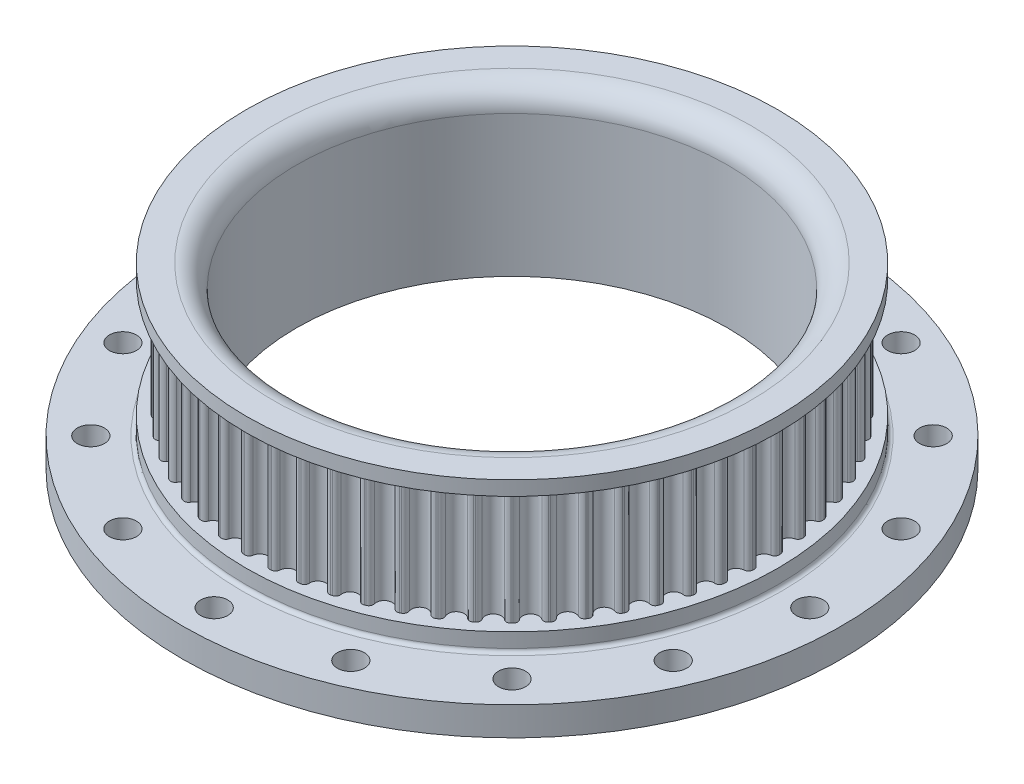
SolidWorks part; units mm, degrees
ref_plane "Front Plane" through (0, 0, 0) normal (0, 0, 1) x (1, 0, 0)
ref_plane "Top Plane" through (0, 0, 0) normal (0, 1, 0) x (1, 0, 0)
ref_plane "Right Plane" through (0, 0, 0) normal (1, 0, 0) x (0, 0, -1)
sketch "Sketch1" plane through (0, 0, 0) normal (0, 1, 0) x (1, 0, 0)
  line L0 (0, 0) -> (0, 28.2667) construction
  line L1 (0, 0) -> (2.9202, 27.7837) construction
  circle A0 centre (0, 0) radius 28.2667 construction
  circle A1 centre (0, 0) radius 27.0467 construction
  circle A2 centre (0, 27.9367) radius 0.89 construction
  circle A5 centre (2.9202, 27.7837) radius 0.89 construction
  arc A6 (0, 27.0467) -> (0.8804, 27.8061) centre (0, 27.9367) ccw
  arc A7 (0.8804, 27.8061) -> (1.3997, 28.2321) centre (1.3749, 27.7327) cw
  arc A8 (1.559, 28.2237) -> (2.031, 27.7458) centre (1.5314, 27.7245) cw
  arc A9 (2.8272, 26.8986) -> (2.031, 27.7458) centre (2.9202, 27.7837) cw
  arc A10 (1.3997, 28.2321) -> (1.559, 28.2237) centre (0, 0) cw
  arc A11 (0, 27.0467) -> (2.8272, 26.8986) centre (0, 0) ccw
  dimension "D1" = 56.5335
  dimension "D3" = 1.78
  dimension "D4" = 0.5
  dimension "D2" = 1.22
  dimension "D5" = 6
extrude "Boss-Extrude1" add sketch "Sketch1" along normal mid plane 13 contours A6 A11 A9 A8 A7 region at (0.001, 0, -0.0192)
ref_axis "Axis1" through (0, 3.3, 0) along (0, -1, 0)
pattern_circular "CirPattern1" count 60 over 360 about axis through (0, 3.3, 0) along (0, -1, 0) of "Boss-Extrude1"
sketch "Sketch2" plane through (0, 0, 0) normal (1, 0, 0) x (0, 0, -1)
  line L10 (0, 6.5) -> (29.4415, 6.5) construction
  line L11 (0, 6.5) -> (0, 8.0875) construction
  line L12 (0, 8.0875) -> (29.4415, 8.0875) construction
  line L15 (29.4415, 6.5) -> (29.4415, 8.0875) construction
  line L20 (0, 3.3) -> (0, -3.3) construction
  line L22 (29.4415, 8.0875) -> (0, 8.0875)
  line L23 (29.4415, 8.0875) -> (29.4415, 6.5)
  line L24 (29.4415, 6.5) -> (0, 6.5)
  line L25 (0, 8.0875) -> (0, 6.5)
  dimension "D1" = 1.5875
  dimension "D2" = 29.4415
  dimension "D3" = 6.5
revolve "Revolve3" add sketch "Sketch2" angle 360 about axis through (0, 3.3, 0) along (0, -1, 0) region at (0, 7.2937, -14.7207)
mirror "Mirror1" about plane through (0, 0, 0) normal (0, 1, 0) of "Revolve3"
sketch "Sketch3" plane through (0, 0, 0) normal (0, -1, 0) x (-1, 0, 0)
  circle A0 centre (0, 0) radius 23.8852
  dimension "D1" = 47.7705
extrude "Cut-Extrude1" cut sketch "Sketch3" against normal through all both and the other way through all
sketch "Sketch5" plane through (0, 0, 0) normal (0, 0, 1) x (1, 0, 0)
  line L0 (29.4415, -6.5) -> (-29.4415, -6.5) construction
  line L1 (-29.854, -8.5) -> (-36.5125, -8.5)
  line L2 (-36.5125, -8.5) -> (-36.5125, -10.0875)
  line L3 (-36.5125, -10.0875) -> (-23.8852, -10.0875)
  line L4 (-23.8852, -10.0875) -> (-23.8852, -8.0875)
  line L5 (-29.4415, -8.0875) -> (29.4415, -8.0875) construction
  line L6 (-23.8852, -8.0875) -> (-29.4415, -8.0875)
  arc A0 (-29.4415, -8.0875) -> (-29.854, -8.5) centre (-29.854, -8.0875) cw
  dimension "D1" = 2
  dimension "D2" = 36.5125
  dimension "D3" = 1.5875
revolve "Revolve4" add sketch "Sketch5" angle 360 about axis through (0, 3.3, 0) along (0, -1, 0)
sketch "Sketch6" plane through (0, -8.5, 0) normal (0, 1, 0) x (1, 0, 0)
  line L0 (-30.488, 12.6286) -> (0, 0) construction
  line L1 (0, 0) -> (-36.5125, 0) construction
  circle A0 centre (-30.488, 12.6286) radius 1.5
  circle A1 centre (0, 0) radius 36.5125 construction
  dimension "D2" = 3
  dimension "D1" = 33
  dimension "D3" = 22.5
extrude "Cut-Extrude2" cut sketch "Sketch6" against normal through all
pattern_circular "CirPattern2" count 16 over 360 about axis through (0, 3.3, 0) along (0, -1, 0) of "Cut-Extrude2"
fillet "Fillet1" radius 2.54 1 edges at (0, 8.0875, -23.8852)
sketch "Sketch9" plane through (0, -10.0875, 0) normal (0, -1, 0) x (1, 0, 0)
  circle A1 centre (0, 0) radius 36.5125
  circle A2 centre (0, 0) radius 29
  circle A3 centre (-30.488, -12.6286) radius 1.5
  circle A4 centre (-30.488, -12.6286) radius 1.5
  circle A5 centre (-23.3345, -23.3345) radius 1.5
  circle A6 centre (-23.3345, -23.3345) radius 1.5
  circle A7 centre (23.3345, 23.3345) radius 1.5
  circle A8 centre (23.3345, 23.3345) radius 1.5
  circle A9 centre (12.6286, 30.488) radius 1.5
  circle A10 centre (12.6286, 30.488) radius 1.5
  circle A11 centre (0, 33) radius 1.5
  circle A12 centre (0, 33) radius 1.5
  circle A13 centre (-12.6286, 30.488) radius 1.5
  circle A14 centre (-12.6286, 30.488) radius 1.5
  circle A15 centre (-23.3345, 23.3345) radius 1.5
  circle A16 centre (-23.3345, 23.3345) radius 1.5
  circle A17 centre (-30.488, 12.6286) radius 1.5
  circle A18 centre (-30.488, 12.6286) radius 1.5
  circle A19 centre (-33, 0) radius 1.5
  circle A20 centre (-33, 0) radius 1.5
  circle A21 centre (30.488, 12.6286) radius 1.5
  circle A22 centre (30.488, 12.6286) radius 1.5
  circle A23 centre (33, 0) radius 1.5
  circle A24 centre (33, 0) radius 1.5
  circle A25 centre (30.488, -12.6286) radius 1.5
  circle A26 centre (30.488, -12.6286) radius 1.5
  circle A27 centre (23.3345, -23.3345) radius 1.5
  circle A28 centre (23.3345, -23.3345) radius 1.5
  circle A29 centre (12.6286, -30.488) radius 1.5
  circle A30 centre (12.6286, -30.488) radius 1.5
  circle A31 centre (0, -33) radius 1.5
  circle A32 centre (0, -33) radius 1.5
  circle A33 centre (-12.6286, -30.488) radius 1.5
  circle A34 centre (-12.6286, -30.488) radius 1.5
  circle A35 centre (0, 0) radius 36.5125
  dimension "D18" = 58
  dimension "D2" = 0
  dimension "D3" = 0
  dimension "D4" = 0
  dimension "D5" = 0
  dimension "D6" = 0
  dimension "D7" = 0
  dimension "D8" = 0
  dimension "D9" = 0
  dimension "D10" = 0
  dimension "D11" = 0
  dimension "D12" = 0
  dimension "D13" = 0
  dimension "D14" = 0
  dimension "D15" = 0
  dimension "D16" = 0
  dimension "D17" = 0
  dimension "D19" = 0
extrude "Boss-Extrude2" add sketch "Sketch9" along normal up to surface (1.5875 mm away)
equation "\"TEETH_NUM\"= 60"
equation "\"TOOTH_PITCH\"= 3mm"
equation "\"PITCH_LINE_OFFSET\"= .015in"
equation "\"DIAMETER_PER_GROOVE\"= \"OUTSIDE_DIAMETER\" / \"TEETH_NUM\" * 1in"
equation "\"PITCH_DIAMETER\"= ( ( \"TEETH_NUM\" * 3 - 1.31 ) / 3.1415 + .415 ) * 1mm"
equation "\"OUTSIDE_DIAMETER\"= \"PITCH_DIAMETER\" - \"PITCH_LINE_OFFSET\" * 2"
equation "\"D1@Sketch1\"=\"OUTSIDE_DIAMETER\""
equation "\"TOOTH_HEIGHT\"= 1.22mm"
equation "\"D2@Sketch1\"=\"TOOTH_HEIGHT\""
equation "\"TOOTH_DIAMETER\"= 1.78mm"
equation "\"INTERNAL_RADIUS\"= .5mm"
equation "\"D3@Sketch1\"=\"TOOTH_DIAMETER\""
equation "\"D5@Sketch1\"=360 / \"TEETH_NUM\""
equation "\"D4@Sketch1\"=\"INTERNAL_RADIUS\""
equation "\"D1@CirPattern1\"=\"TEETH_NUM\""
equation "\"BELT_GAP\"= 13mm"
equation "\"D2@Sketch2\"=\"PITCH_DIAMETER\"/2+1/32"
equation "\"D3@Sketch2\"=\"BELT_GAP\"/2"
equation "\"D1@Sketch3\"=\"PITCH_DIAMETER\"-.375"
equation "\"D1@Boss-Extrude1\"=\"BELT_GAP\""
equation "\"center_offset\"=0.75"
equation "\"Bearing_Diameter\"= 58mm"
equation "\"bolt_on_feature\"=16"
equation "\"D1@CirPattern2\"=\"bolt_on_feature\""
